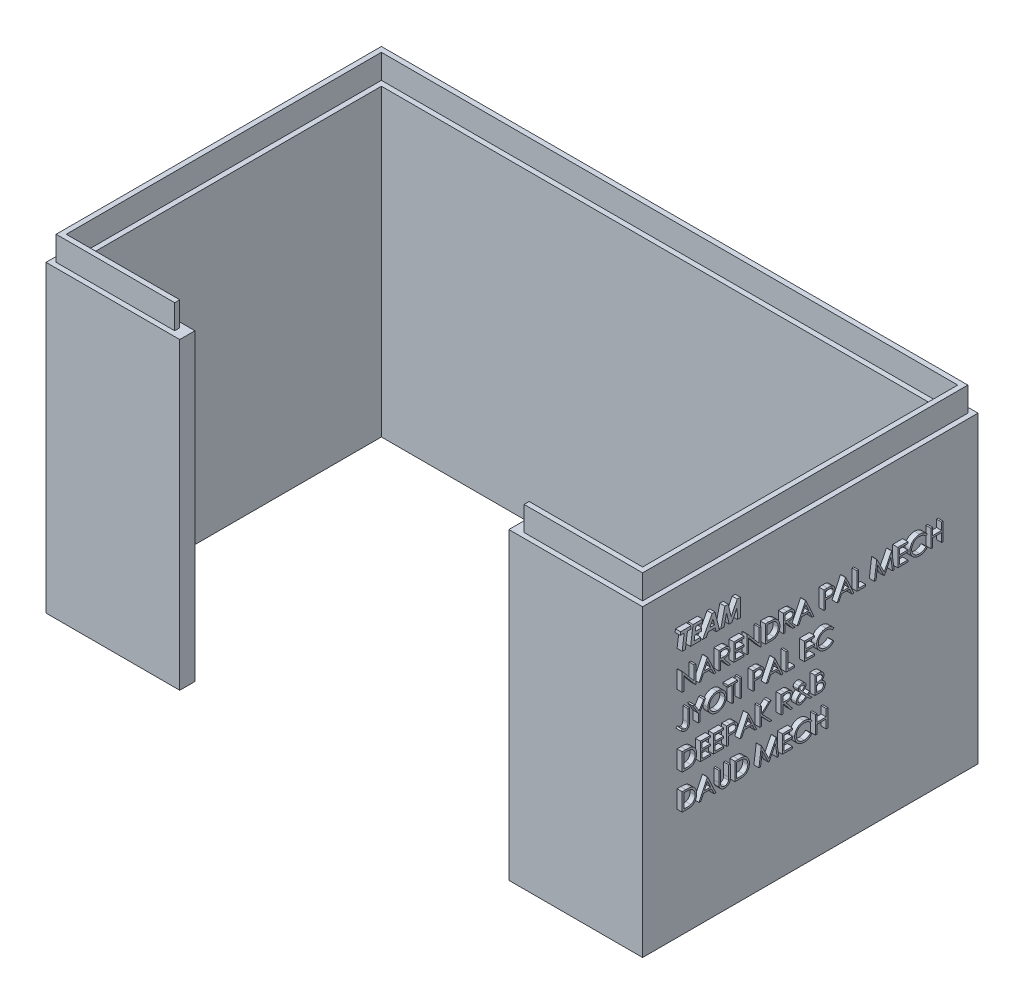
SolidWorks part; units mm, degrees
ref_plane "Front Plane" through (0, 0, 0) normal (0, 0, 1) x (1, 0, 0)
ref_plane "Top Plane" through (0, 0, 0) normal (0, 1, 0) x (1, 0, 0)
ref_plane "Right Plane" through (0, 0, 0) normal (1, 0, 0) x (0, 0, -1)
sketch "Sketch1" plane through (0, 0, 0) normal (0, 1, 0) x (1, 0, 0)
  line L0 (-32.5, -30.12) -> (-32.5, -33.12)
  line L1 (55.915, -30.12) -> (32.5, -30.12)
  line L2 (55.915, -30.12) -> (55.915, 30.12)
  line L3 (55.915, 30.12) -> (-55.915, 30.12)
  line L4 (-55.915, -30.12) -> (-55.915, 30.12)
  line L5 (55.915, -30.12) -> (-55.915, 30.12) construction
  line L6 (55.915, 30.12) -> (-55.915, -30.12) construction
  line L7 (58.915, -33.12) -> (32.5, -33.12)
  line L8 (58.915, -33.12) -> (58.915, 33.12)
  line L9 (58.915, 33.12) -> (-58.915, 33.12)
  line L10 (-58.915, -33.12) -> (-58.915, 33.12)
  line L11 (58.915, -33.12) -> (-58.915, 33.12) construction
  line L12 (58.915, 33.12) -> (-58.915, -33.12) construction
  line L13 (0, 0) -> (0, -50000) construction
  line L14 (32.5, -30.12) -> (32.5, -33.12)
  line L15 (-32.5, -30.12) -> (-55.915, -30.12)
  line L16 (-32.5, -33.12) -> (-58.915, -33.12)
  point P0 (0, 0)
  point P6 (0, 0)
  dimension "D1" = 3
  dimension "D2" = 3
  dimension "D3" = 60.24
  dimension "D4" = 111.83
  dimension "D5" = 65
extrude "Boss-Extrude1" add sketch "Sketch1" along normal blind 60
sketch "Sketch3" plane through (0, 60, 0) normal (0, 1, 0) x (1, 0, 0)
  line L0 (-55.915, -30.12) -> (-55.915, 30.12) construction
  line L1 (57.915, -32.12) -> (34.5, -32.12)
  line L2 (57.915, -32.12) -> (57.915, 32.12)
  line L3 (57.915, 32.12) -> (-57.915, 32.12)
  line L4 (-57.915, -32.12) -> (-57.915, 32.12)
  line L5 (57.915, -32.12) -> (-57.915, 32.12) construction
  line L6 (57.915, 32.12) -> (-57.915, -32.12) construction
  line L7 (56.915, -31.12) -> (34.5, -31.12)
  line L8 (56.915, -31.12) -> (56.915, 31.12)
  line L9 (56.915, 31.12) -> (-56.915, 31.12)
  line L10 (-56.915, -31.12) -> (-56.915, 31.12)
  line L11 (56.915, -31.12) -> (-56.915, 31.12) construction
  line L12 (56.915, 31.12) -> (-56.915, -31.12) construction
  line L13 (-55.915, 30.12) -> (55.915, 30.12) construction
  line L14 (0, 0) -> (0, -32.12) construction
  line L15 (-34.5, -31.12) -> (-34.5, -32.12)
  line L16 (-32.5, -33.12) -> (-32.5, -30.12) construction
  line L17 (34.5, -31.12) -> (34.5, -32.12)
  line L18 (-34.5, -31.12) -> (-56.915, -31.12)
  line L19 (-34.5, -32.12) -> (-57.915, -32.12)
  line L20 (32.5, -30.12) -> (32.5, -33.12) construction
  point P0 (0, 0)
  point P6 (0, 0)
  point P16 (-34.5, -31.62)
  dimension "D1" = 1
  dimension "D2" = 1
  dimension "D3" = 1
  dimension "D4" = 1
  dimension "D5" = 2
  dimension "D6" = 2
extrude "Boss-Extrude2" add sketch "Sketch3" along normal blind 4.8
sketch "Sketch4" plane through (0, 0, 0) normal (0, -1, 0) x (1, 0, 0)
  line L0 (-34.6, 32.22) -> (-34.6, 31.02)
  line L1 (56.815, -31.02) -> (-56.815, -31.02)
  line L2 (56.815, -31.02) -> (56.815, 31.02)
  line L3 (56.815, 31.02) -> (34.6, 31.02)
  line L4 (-56.815, -31.02) -> (-56.815, 31.02)
  line L5 (56.815, -31.02) -> (-56.815, 31.02) construction
  line L6 (56.815, 31.02) -> (-56.815, -31.02) construction
  line L7 (58.015, -32.22) -> (-58.015, -32.22)
  line L8 (58.015, -32.22) -> (58.015, 32.22)
  line L9 (58.015, 32.22) -> (34.6, 32.22)
  line L10 (-58.015, -32.22) -> (-58.015, 32.22)
  line L11 (58.015, -32.22) -> (-58.015, 32.22) construction
  line L12 (58.015, 32.22) -> (-58.015, -32.22) construction
  line L14 (34.6, 32.22) -> (34.6, 31.02)
  line L15 (-55.915, 30.12) -> (-55.915, -30.12) construction
  line L16 (-32.5, 30.12) -> (-55.915, 30.12) construction
  line L17 (-32.5, 33.12) -> (-32.5, 30.12) construction
  line L18 (32.5, 30.12) -> (32.5, 33.12) construction
  line L19 (-34.6, 32.22) -> (-58.015, 32.22)
  line L20 (-34.6, 31.02) -> (-56.815, 31.02)
  point P0 (0, 0)
  point P6 (0, 0)
  dimension "D1" = 0.9
  dimension "D2" = 1.2
  dimension "D3" = 1.2
  dimension "D4" = 0.9
  dimension "D5" = 2.1
  dimension "D6" = 2.1
extrude "Cut-Extrude1" cut sketch "Sketch4" against normal blind 5
sketch "Sketch5" plane through (58.915, 0, 0) normal (1, 0, 0) x (0, 0, -1)
  line L0 (0, 60) -> (0, -49940) construction
  line L1 (-33.12, 60) -> (33.12, 60) construction
  line L2 (-33.12, 30) -> (49966.88, 30) construction
  line L3 (-33.12, 60) -> (-33.12, 0) construction
  line L5 (-26.7555, 49.4751) -> (26.7555, 49.4751) construction
  line L6 (-26.7555, 49.4751) -> (-26.7555, 10.5249) construction
  line L7 (-26.7555, 10.5249) -> (26.7555, 10.5249) construction
  line L8 (26.7555, 49.4751) -> (26.7555, 10.5249) construction
  text T0 "<b><i>TEAM</i></b>\r\nNARENDRA PAL MECH\r\nJYOTI PAL EC\r\nDEEPAK R&B\r\nDAUD MECH"
  point P4 (0, 60)
  point P9 (-33.12, 30)
  point P14 (0, 49.4751)
  point P15 (-26.7555, 30)
  point P16 (0, 0)
extrude "Boss-Extrude3" add sketch "Sketch5" along normal blind 1
